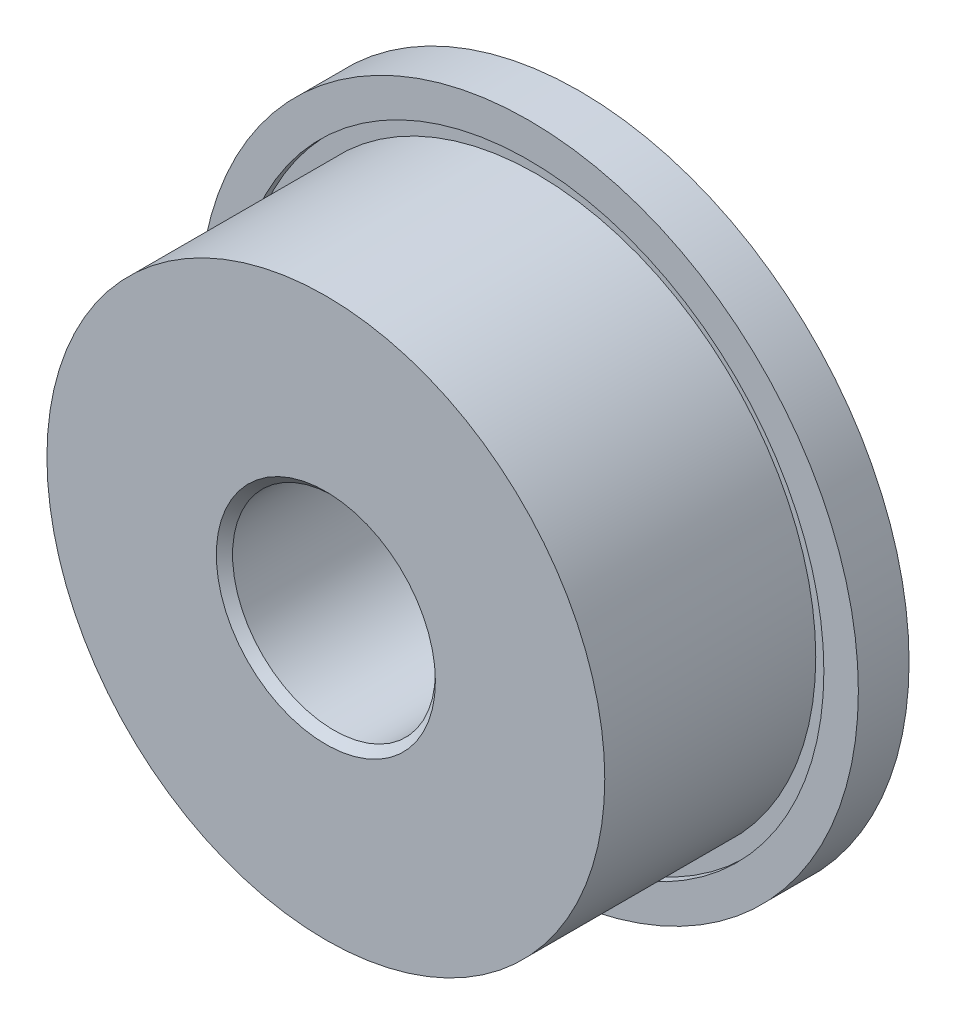
SolidWorks part; units mm, degrees
ref_plane "Front Plane" through (0, 0, 0) normal (0, 0, 1) x (1, 0, 0)
ref_plane "Top Plane" through (0, 0, 0) normal (0, 1, 0) x (1, 0, 0)
ref_plane "Right Plane" through (0, 0, 0) normal (1, 0, 0) x (0, 0, -1)
sketch "Sketch1" plane through (0, 0, 0) normal (0, 0, 1) x (1, 0, 0)
  circle A0 centre (0, 0) radius 10.3187
  dimension "D1" = 20.6375
extrude "Boss-Extrude1" add sketch "Sketch1" along normal blind 1.5875
sketch "Sketch2" plane through (0, 0, 1.5875) normal (0, 0, 1) x (1, 0, 0)
  circle A0 centre (0, 0) radius 8.7312
  dimension "D1" = 17.4625
extrude "Boss-Extrude2" add sketch "Sketch2" along normal blind 6.35
sketch "Sketch3" plane through (0, 0, 0) normal (0, 0, -1) x (-1, 0, 0)
  circle A0 centre (0, 0) radius 6.35
  dimension "D1" = 12.7
extrude "Boss-Extrude3" add sketch "Sketch3" along normal blind 1.5875
sketch "Sketch4" plane through (0, 0, -1.5875) normal (0, 0, -1) x (-1, 0, 0)
  circle A0 centre (0, 0) radius 4.7625
  circle A1 centre (0, 0) radius 3.9688
  dimension "D1" = 9.525
  dimension "D2" = 7.9375
extrude "Cut-Extrude1" cut sketch "Sketch4" against normal blind 0.254
sketch "Sketch5" plane through (0, 0, 1.5875) normal (0, 0, 1) x (1, 0, 0)
  circle A0 centre (0, 0) radius 8.7312
  circle A1 centre (0, 0) radius 9.2392
  circle A2 centre (0, 0) radius 8.7312 construction
  dimension "D1" = 0.508
  dimension "D2" = 17.4625
extrude "Cut-Extrude2" cut sketch "Sketch5" against normal blind 0.254
sketch "Sketch6" plane through (0, 0, 7.9375) normal (0, 0, 1) x (1, 0, 0)
  circle A0 centre (0, 0) radius 3.175
  dimension "D1" = 6.35
extrude "Cut-Extrude3" cut sketch "Sketch6" against normal through all
chamfer "Chamfer1" distance 0.254 angle 45 3 edges at (-3.9688, 0, -1.5875) (3.175, 0, -1.5875) (3.175, 0, 7.9375)
